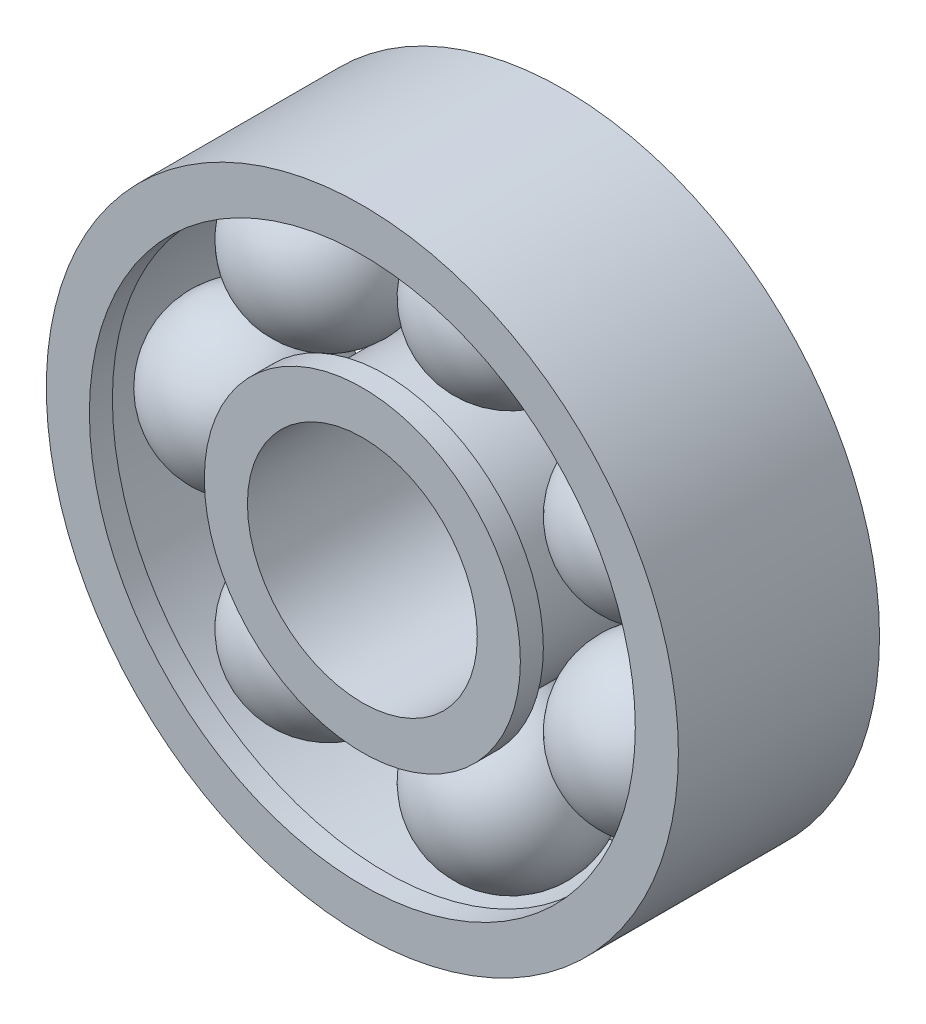
SolidWorks part; units mm, degrees
ref_plane "Front Plane" through (0, 0, 0) normal (0, 0, 1) x (1, 0, 0)
ref_plane "Top Plane" through (0, 0, 0) normal (0, 1, 0) x (1, 0, 0)
ref_plane "Right Plane" through (0, 0, 0) normal (1, 0, 0) x (0, 0, -1)
sketch "Sketch1" plane through (0, 0, 0) normal (0, 0, 1) x (1, 0, 0)
  circle A0 centre (0, 0) radius 4
  circle A1 centre (0, 0) radius 5.5
  circle A2 centre (0, 0) radius 11
  circle A3 centre (0, 0) radius 9.5
extrude "Boss-Extrude1" add sketch "Sketch1" along normal blind 3.5 and the other way blind 3.5 contours A2 A3 | A1 A0 region at (-5.3444, 0, 0) region at (-10.6889, 0, 0)
sketch "Sketch2" plane through (0, 0, 0) normal (0, 0, 1) x (1, 0, 0)
  circle A0 centre (0, 0) radius 4.6977
  circle A1 centre (0, 0) radius 10.3
extrude "Cut-Extrude1" cut sketch "Sketch2" against normal blind 2.7 and the other way blind 2.7
sketch "Sketch4" plane through (0, 0, 0) normal (0, 0, 1) x (1, 0, 0)
  line L0 (-4.6977, 0) -> (-10.3, 0) construction
  line L1 (3.85, 0) -> (-3.85, 0) construction
  line L2 (-7.4988, 0) -> (-7.4988, 2.8)
  line L3 (-7.4988, 0) -> (-7.4988, -2.8)
  line L4 (-4.6754, 5.8628) -> (-2.4863, 7.6086)
  line L5 (-4.6754, 5.8628) -> (-6.8646, 4.1171)
  line L6 (1.6686, 7.3108) -> (4.3984, 6.6878)
  line L7 (1.6686, 7.3108) -> (-1.0612, 7.9339)
  line L8 (6.7562, 3.2536) -> (7.9711, 0.7309)
  line L9 (6.7562, 3.2536) -> (5.5413, 5.7763)
  line L10 (6.7562, -3.2536) -> (5.5413, -5.7763)
  line L11 (6.7562, -3.2536) -> (7.9711, -0.7309)
  line L12 (1.6686, -7.3108) -> (-1.0612, -7.9339)
  line L13 (1.6686, -7.3108) -> (4.3984, -6.6878)
  line L14 (-4.6754, -5.8628) -> (-6.8646, -4.1171)
  line L15 (-4.6754, -5.8628) -> (-2.4863, -7.6086)
  circle A0 centre (0, 0) radius 4.6977 construction
  circle A1 centre (0, 0) radius 10.3 construction
  arc A2 (-7.4988, -2.8) -> (-7.4988, 2.8) centre (-7.4988, 0) ccw
  arc A3 (-6.8646, 4.1171) -> (-2.4863, 7.6086) centre (-4.6754, 5.8628) ccw
  arc A4 (-1.0612, 7.9339) -> (4.3984, 6.6878) centre (1.6686, 7.3108) ccw
  arc A5 (5.5413, 5.7763) -> (7.9711, 0.7309) centre (6.7562, 3.2536) ccw
  arc A6 (7.9711, -0.7309) -> (5.5413, -5.7763) centre (6.7562, -3.2536) ccw
  arc A7 (4.3984, -6.6878) -> (-1.0612, -7.9339) centre (1.6686, -7.3108) ccw
  arc A8 (-2.4863, -7.6086) -> (-6.8646, -4.1171) centre (-4.6754, -5.8628) ccw
  point P38 (0, 0)
  dimension "D1" = 7
revolve "Revolve2" add sketch "Sketch4" angle 360 about L2 region at (-6.3105, -1.1884, 0) region at (-6.3105, 1.1884, 0)
revolve "Revolve3" add sketch "Sketch4<7>" angle 360 about L4 region at (-3.9345, 4.9337, 0)
sketch "Sketch4<7>" plane through (0, 0, 0) normal (0, 0, 1) x (1, 0, 0) same geometry as "Sketch4"
revolve "Revolve4" add sketch "Sketch4<8>" angle 360 about L6 region at (1.4042, 6.1523, 0)
sketch "Sketch4<8>" plane through (0, 0, 0) normal (0, 0, 1) x (1, 0, 0) same geometry as "Sketch4"
revolve "Revolve5" add sketch "Sketch4<9>" angle 360 about L9 region at (5.6855, 2.738, 0)
sketch "Sketch4<9>" plane through (0, 0, 0) normal (0, 0, 1) x (1, 0, 0) same geometry as "Sketch4"
revolve "Revolve6" add sketch "Sketch4<10>" angle 360 about L11 region at (5.6855, -2.738, 0)
sketch "Sketch4<10>" plane through (0, 0, 0) normal (0, 0, 1) x (1, 0, 0) same geometry as "Sketch4"
revolve "Revolve7" add sketch "Sketch4<11>" angle 360 about L13 region at (1.4042, -6.1523, 0)
sketch "Sketch4<11>" plane through (0, 0, 0) normal (0, 0, 1) x (1, 0, 0) same geometry as "Sketch4"
revolve "Revolve8" add sketch "Sketch4<12>" angle 360 about L14 region at (-3.9345, -4.9337, 0)
sketch "Sketch4<12>" plane through (0, 0, 0) normal (0, 0, 1) x (1, 0, 0) same geometry as "Sketch4"
